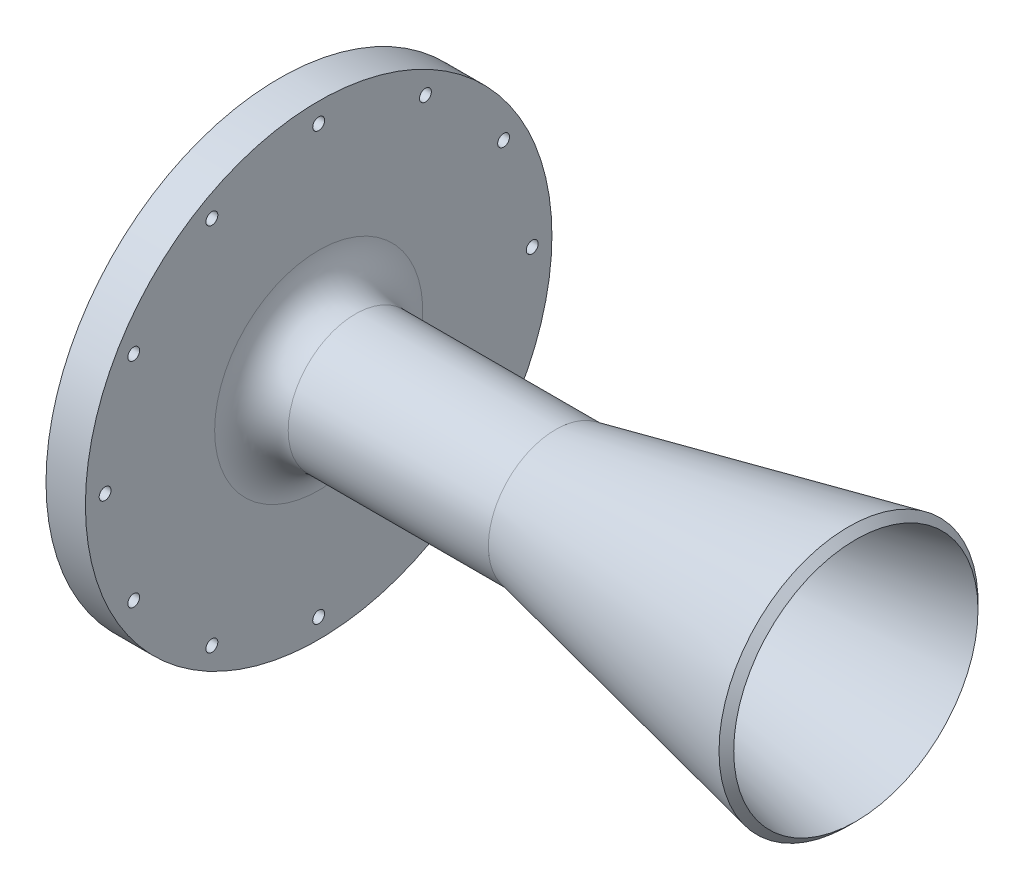
SolidWorks part; units mm, degrees
material "Stainless Steel (ferritic)"
ref_plane "Front Plane" through (0, 0, 0) normal (0, 0, 1) x (1, 0, 0)
ref_plane "Top Plane" through (0, 0, 0) normal (0, 1, 0) x (1, 0, 0)
ref_plane "Right Plane" through (0, 0, 0) normal (1, 0, 0) x (0, 0, -1)
sketch "Sketch2" plane through (0, 0, 0) normal (0, 0, 1) x (1, 0, 0)
  line L0 (0, 0) -> (165.0115, 0) construction
  line L1 (0, 20.5835) -> (0, 56.388)
  line L2 (0, 56.388) -> (9.525, 56.388)
  line L3 (9.525, 56.388) -> (9.525, 16.256)
  line L11 (66.8065, 16.256) -> (139.7, 31.75)
  line L17 (139.7, 31.75) -> (139.7, 29.5925)
  line L18 (60.325, 12.7208) -> (60.325, 14.351)
  line L19 (60.325, 14.351) -> (10.795, 14.351)
  line L20 (0, 20.5835) -> (10.795, 14.351)
  line L21 (60.325, 12.7208) -> (139.7, 29.5925)
  line L22 (9.525, 16.256) -> (66.8065, 16.256)
  dimension "D2" = 9.525
  dimension "D3" = 1.905
  dimension "D4" = 10.795
  dimension "D5" = 14.351
  dimension "D6" = 31.75
  dimension "D7" = 12
  dimension "D8" = 139.7
  dimension "D9" = 1.6302
  dimension "D10" = 30
  dimension "D11" = 56.388
  dimension "D12" = 49.53
revolve "Main Structure" add sketch "Sketch2" angle 360 about L0
sketch "Sketch4" plane through (0, 0, 0) normal (-1, 0, 0) x (0, 0, 1)
  circle A0 centre (0, 0) radius 51.6255 construction
  circle A1 centre (0, -51.6255) radius 2.146
  circle A2 centre (-25.8127, -44.709) radius 2.146
  circle A3 centre (-44.709, -25.8128) radius 2.146
  circle A4 centre (-51.6255, 0) radius 2.146
  circle A5 centre (-44.709, 25.8127) radius 2.146
  circle A6 centre (-25.8128, 44.709) radius 2.146
  circle A7 centre (0, 51.6255) radius 2.146
  circle A8 centre (25.8127, 44.709) radius 2.146
  circle A9 centre (44.709, 25.8128) radius 2.146
  circle A10 centre (51.6255, 0) radius 2.146
  circle A11 centre (44.709, -25.8127) radius 2.146
  circle A12 centre (25.8128, -44.709) radius 2.146
  point P29 (0, 0)
  dimension "D1" = 12
  dimension "D2" = 103.251
hole_wizard "Flange Holes" positions "Sketch7" profile "Sketch8" hole size "#33" standard "ANSI Inch" end condition up to next
sketch "Sketch7" plane through (0, 0, 0) normal (-1, 0, 0) x (0, 0, 1)
  point P0 (0, -51.6255)
  point P3 (-25.8127, -44.709)
  point P6 (-44.709, -25.8128)
  point P9 (-51.6255, 0)
  point P12 (-44.709, 25.8127)
  point P15 (-25.8128, 44.709)
  point P18 (0, 51.6255)
  point P21 (25.8127, 44.709)
  point P24 (44.709, 25.8128)
  point P27 (51.6255, 0)
  point P30 (44.709, -25.8127)
  point P33 (25.8128, -44.709)
sketch "Sketch8" plane through (0, -51.6255, 0) normal (0, 1, 0) x (0, 0, 1)
  line L0 (0, 0) -> (0, 9.525)
  line L1 (0, 9.525) -> (1.4351, 9.525)
  line L2 (1.4351, 9.525) -> (1.4351, 0)
  line L5 (1.4351, 0) -> (0, 0)
  line L11 (0, -6.35) -> (0, 107.95) construction
  dimension "Thru Hole Dia." = 2.8702
  dimension "Thru Hole Depth" = 9.525
sketch "Sketch9" plane through (0, 0, 0) normal (-1, 0, 0) x (0, 0, 1)
  line L0 (0, 0) -> (-67.6727, 18.1329) construction
  line L1 (0, 0) -> (-51.6255, 0) construction
  circle A0 centre (0, 0) radius 51.6255 construction
  circle A1 centre (-49.8664, 13.3617) radius 2.9451
  circle A2 centre (49.8664, -13.3617) radius 2.9451
  point P14 (0, 0)
  dimension "D1" = 15
  dimension "D2" = 2
hole_wizard "Dowel Holes" positions "Sketch10" profile "Sketch11" hole size "3/16" standard "ANSI Inch"
sketch "Sketch10" plane through (0, 0, 0) normal (-1, 0, 0) x (0, 0, 1)
  point P0 (49.8664, -13.3617)
  point P3 (-49.8664, 13.3617)
sketch "Sketch11" plane through (0, -13.3617, 49.8664) normal (0, 1, 0) x (0, 0, 1)
  line L0 (0, 0) -> (0, 7.7808)
  line L1 (0, 7.7808) -> (2.3812, 6.35)
  line L2 (2.3812, 6.35) -> (2.3812, 0)
  line L5 (2.3812, 0) -> (0, 0)
  line L10 (0, 7.7808) -> (-2.3812, 6.35) construction
  line L11 (0, -6.35) -> (0, 107.95) construction
  dimension "Hole Dia." = 4.7625
  dimension "Hole Depth" = 6.35
  dimension "Drill Angle" = 118
fillet "Fillet1" radius 8.89 1 edges at (9.525, 0, 16.256)
sketch "Sketch13" plane through (0, 0, 0) normal (0, 1, 0) x (1, 0, 0)
  line L0 (0, 38.1) -> (3.3333, 0)
  line L1 (0, 56.388) -> (0, -56.388) construction
  line L2 (3.3333, 0) -> (0, 0)
  line L3 (0, 0) -> (0, 38.1)
  dimension "D1" = 38.1
  dimension "D2" = 5
revolve "Cut-Revolve1" cut sketch "Sketch13" angle 360 about L2
chamfer "Chamfer1" distance 2.54 angle 45 1 edges at (139.7, 0, 31.75) first distance on face at (139.7, 0, 31.75)
